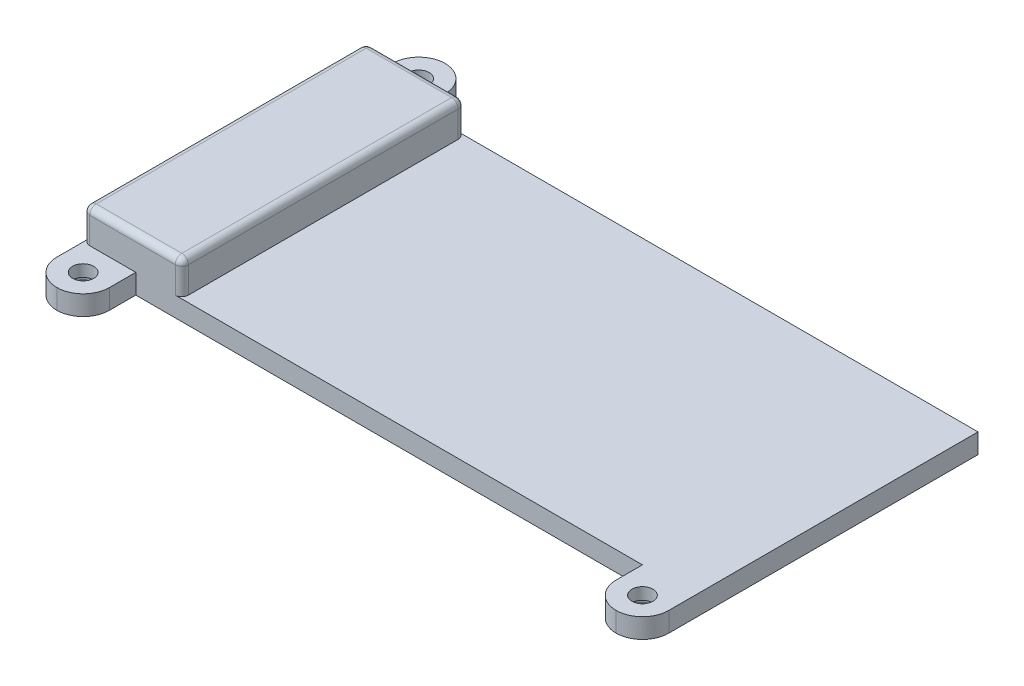
SolidWorks part; units mm, degrees
ref_plane "前视基准面" through (0, 0, 0) normal (0, 0, 1) x (1, 0, 0)
ref_plane "上视基准面" through (0, 0, 0) normal (0, 1, 0) x (1, 0, 0)
ref_plane "右视基准面" through (0, 0, 0) normal (1, 0, 0) x (0, 0, -1)
other "Configuration Table"
sketch "草图1" plane through (0, 0, 0) normal (0, 1, 0) x (1, 0, 0)
  line L0 (-38.5, -21.5) -> (38.5, -21.5)
  line L5 (-46.5, -21.5) -> (-46.5, 21.5)
  line L6 (-38.5, 21.5) -> (38.5, 21.5)
  line L7 (46.5, -21.5) -> (46.5, 21.5)
  line L8 (-46.5, -21.5) -> (46.5, 21.5) construction
  line L9 (-46.5, 21.5) -> (46.5, -21.5) construction
  line L10 (0, 0) -> (0, 21.5) construction
  line L12 (46.5, 21.5) -> (46.5, 29.5)
  line L13 (46.5, 29.5) -> (38.5, 29.5)
  line L14 (38.5, 21.5) -> (38.5, 29.5)
  line L15 (0, 0) -> (46.5, 0) construction
  line L16 (46.5, -29.5) -> (38.5, -29.5)
  line L17 (38.5, -21.5) -> (38.5, -29.5)
  line L19 (46.5, -21.5) -> (46.5, -29.5)
  line L21 (-38.5, -21.5) -> (-38.5, -29.5)
  line L22 (-46.5, -29.5) -> (-38.5, -29.5)
  line L23 (-46.5, -21.5) -> (-46.5, -29.5)
  line L24 (-46.5, 29.5) -> (-38.5, 29.5)
  line L25 (-38.5, 21.5) -> (-38.5, 29.5)
  line L27 (-46.5, 21.5) -> (-46.5, 29.5)
  point P0 (0, 0)
  dimension "D1" = 43
  dimension "D2" = 93
  dimension "D3" = 8
  dimension "D4" = 8
extrude "凸台-拉伸1" add sketch "草图1" along normal blind 3
fillet "圆角1" radius 4 8 edges at (38.5, 1.5, 29.5) (46.5, 1.5, 29.5) (-46.5, 1.5, 29.5) (-38.5, 1.5, 29.5) (-46.5, 1.5, -29.5) (-38.5, 1.5, -29.5) (38.5, 1.5, -29.5) (46.5, 1.5, -29.5)
sketch "草图2" plane through (0, 0, 0) normal (0, -1, 0) x (1, 0, 0)
  line L0 (0, 0) -> (0, 21.5) construction
  line L1 (-38.5, 21.5) -> (38.5, 21.5) construction
  line L2 (0, 0) -> (46.5, 0) construction
  line L3 (46.5, 25.5) -> (46.5, -25.5) construction
  circle A0 centre (42.5, 25.5) radius 1.6
  circle A2 centre (42.5, -25.5) radius 1.6
  circle A3 centre (-42.5, -25.5) radius 1.6
  circle A4 centre (-42.5, 25.5) radius 1.6
  dimension "D1" = 3.2
extrude "切除-拉伸1" cut sketch "草图2" against normal blind 3
sketch "草图3" plane through (0, 0, 0) normal (0, -1, 0) x (1, 0, 0)
  line L0 (0, 0) -> (46.5, 0) construction
  line L1 (0, 21.5) -> (0, 0.3593) construction
  line L2 (-38.5, 21.5) -> (38.5, 21.5) construction
  line L3 (0, 0) -> (0, 21.5) construction
  circle A4 centre (-42.5, 25.5) radius 2.8
  circle A5 centre (42.5, 25.5) radius 2.8
  circle A6 centre (42.5, 25.5) radius 2.8
  circle A7 centre (42.5, -25.5) radius 2.8
  circle A8 centre (-42.5, -25.5) radius 2.8
  dimension "D1" = 1.2
extrude "切除-拉伸2" cut sketch "草图3" against normal blind 1.2
sketch "草图4" plane through (0, 3, 0) normal (0, 1, 0) x (1, 0, 0)
  line L0 (38.5, 21.5) -> (-38.5, 21.5) construction
  line L1 (-31.5, 21.5) -> (-46.5, 21.5)
  line L2 (-31.5, 21.5) -> (-31.5, -21.5)
  line L3 (-31.5, -21.5) -> (-46.5, -21.5)
  line L4 (-46.5, 21.5) -> (-46.5, -21.5)
  line L5 (-46.5, 25.5) -> (-46.5, -25.5) construction
  line L6 (-38.5, -21.5) -> (38.5, -21.5) construction
  dimension "D1" = 15
extrude "凸台-拉伸2" add sketch "草图4" along normal blind 5
fillet "圆角2" radius 1 8 edges at (-39, 8, 21.5) (-46.5, 8, 0) (-39, 8, -21.5) (-31.5, 8, 0) (-31.5, 5.5, 21.5) (-46.5, 5.5, 21.5) (-31.5, 5.5, -21.5) (-46.5, 5.5, -21.5)
sketch "草图5" plane through (0, 0, 0) normal (0, -1, 0) x (1, 0, 0)
  line L0 (38.5, -21.5) -> (-38.5, -21.5) construction
  line L2 (31.0551, -21.5) -> (52.973, -21.5)
  line L3 (31.0551, -21.5) -> (31.0551, -33.053)
  line L4 (31.0551, -33.053) -> (52.973, -33.053)
  line L5 (52.973, -21.5) -> (52.973, -33.053)
extrude "切除-拉伸3" cut sketch "草图5" against normal blind 10
